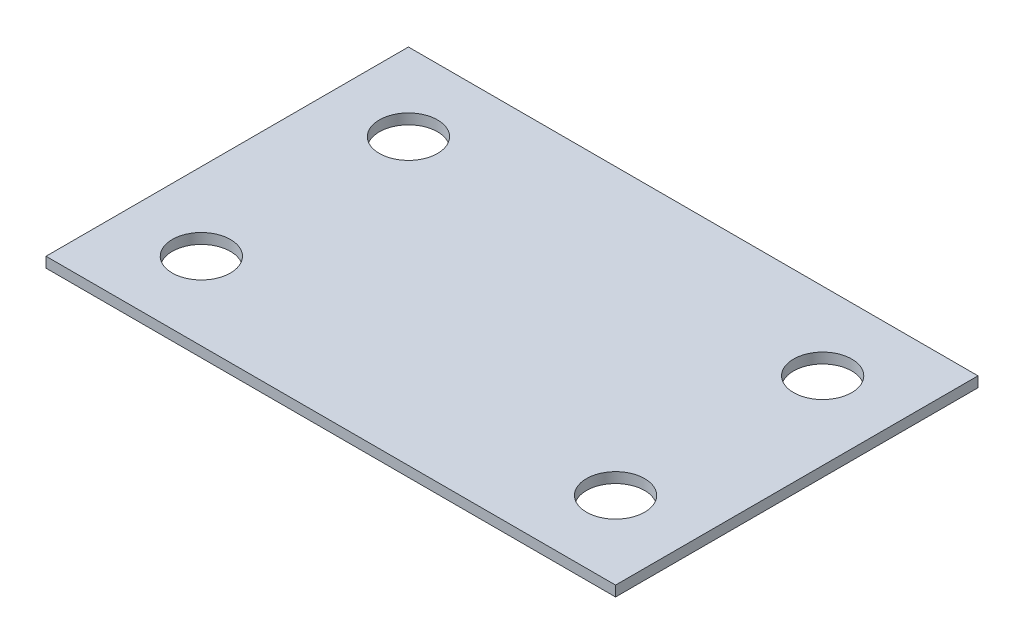
SolidWorks part; units mm, degrees
ref_plane "Front Plane" through (0, 0, 0) normal (0, 0, 1) x (1, 0, 0)
ref_plane "Top Plane" through (0, 0, 0) normal (0, 1, 0) x (1, 0, 0)
ref_plane "Right Plane" through (0, 0, 0) normal (1, 0, 0) x (0, 0, -1)
sketch "Sketch1" plane through (0, 0, 0) normal (0, 1, 0) x (1, 0, 0)
  line L0 (9.525, 34.925) -> (0, 34.925) construction
  line L1 (0, 0) -> (69.85, 0)
  line L2 (0, 0) -> (0, 44.45)
  line L3 (0, 44.45) -> (69.85, 44.45)
  line L4 (69.85, 0) -> (69.85, 44.45)
  line L5 (9.525, 34.925) -> (60.325, 34.925) construction
  line L6 (9.525, 34.925) -> (9.525, 9.525) construction
  line L7 (9.525, 9.525) -> (60.325, 9.525) construction
  line L8 (60.325, 34.925) -> (60.325, 9.525) construction
  line L9 (9.525, 34.925) -> (9.525, 44.45) construction
  circle A0 centre (9.525, 34.925) radius 3.5687
  circle A1 centre (60.325, 34.925) radius 3.5687
  circle A2 centre (9.525, 9.525) radius 3.5687
  circle A3 centre (60.325, 9.525) radius 3.5687
  point P13 (34.925, 34.925)
  point P14 (34.925, 44.45)
  dimension "D5" = 7.1374
  dimension "D1" = 69.85
  dimension "D2" = 44.45
  dimension "D3" = 50.8
  dimension "D4" = 25.4
extrude "Boss-Extrude1" add sketch "Sketch1" along normal blind 1.27
